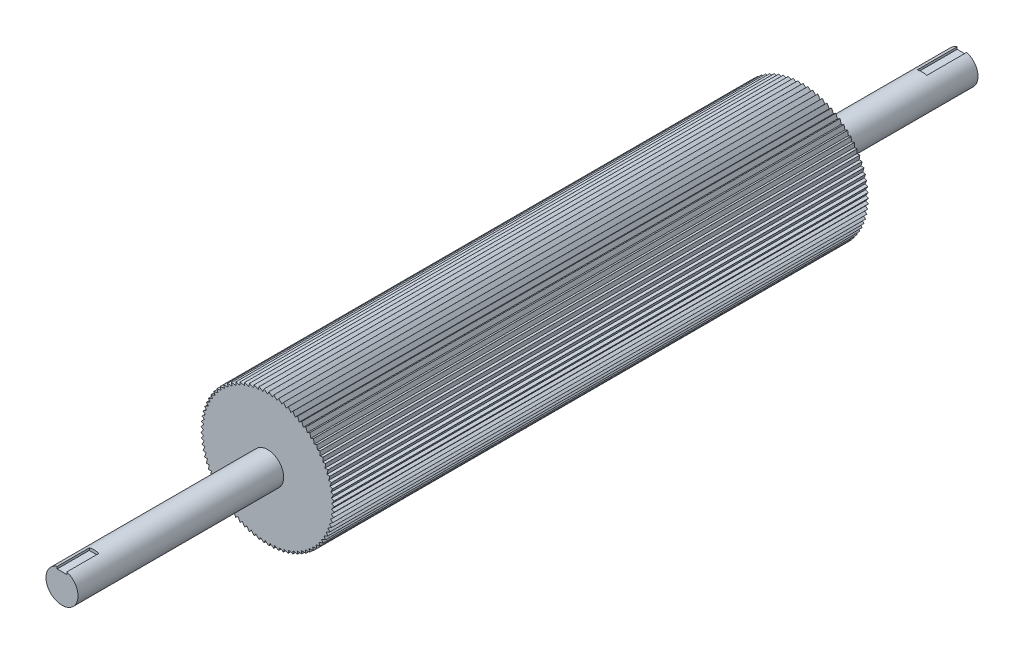
SolidWorks part; units mm, degrees
material "AISI 1020 Steel, Cold Rolled"
ref_plane "Front Plane" through (0, 0, 0) normal (0, 0, 1) x (1, 0, 0)
ref_plane "Top Plane" through (0, 0, 0) normal (0, 1, 0) x (1, 0, 0)
ref_plane "Right Plane" through (0, 0, 0) normal (1, 0, 0) x (0, 0, -1)
sketch "Sketch2" plane through (0, 0, 0) normal (0, 0, 1) x (1, 0, 0)
  circle A0 centre (0, 0) radius 125
  dimension "D1" = 250
extrude "Boss-Extrude1" add sketch "Sketch2" along normal mid plane 1000
sketch "Sketch3" plane through (0, 0, 500) normal (0, 0, 1) x (1, 0, 0)
  circle A0 centre (0, 0) radius 30
  dimension "D1" = 60
extrude "Boss-Extrude2" add sketch "Sketch3" along normal blind 385
sketch "Sketch4" plane through (0, 0, -500) normal (0, 0, -1) x (-1, 0, 0)
  circle A0 centre (0, 0) radius 30
  dimension "D1" = 60
extrude "Boss-Extrude3" add sketch "Sketch4" along normal blind 300
sketch "Sketch11" plane through (0, 0, 500) normal (0, 0, 1) x (1, 0, 0)
  line L0 (0, 14.8002) -> (0, 125) construction
sketch "Sketch12" plane through (0, 0, 885) normal (0, 0, 1) x (1, 0, 0)
  line L1 (-9, 24.5) -> (9, 24.5)
  line L2 (-9, 24.5) -> (-9, 35.5)
  line L3 (-9, 35.5) -> (9, 35.5)
  line L4 (9, 24.5) -> (9, 35.5)
  line L5 (-9, 24.5) -> (9, 35.5) construction
  line L6 (-9, 35.5) -> (9, 24.5) construction
  circle A0 centre (0, 0) radius 30 construction
  circle A1 centre (0, 0) radius 30 construction
  point P0 (0, 30)
  dimension "D1" = 18
  dimension "D2" = 5.5
extrude "Cut-Extrude5" cut sketch "Sketch12" against normal blind 60
sketch "Sketch15" plane through (0, 0, 500) normal (0, 0, 1) x (1, 0, 0)
  line L0 (0, 120) -> (2.3215, 124.9784)
  line L1 (0, 14.8002) -> (0, 125) construction
  line L2 (0, 120) -> (-6.8709, 124.811)
  circle A1 centre (0, 0) radius 125
  arc A2 (2.3215, 124.9784) -> (-6.8709, 124.811) centre (0, 0) ccw
  dimension "D4" = 120
  dimension "D2" = 25
  dimension "D3" = 55
  dimension "D1" = 0
extrude "Cut-Extrude6" cut sketch "Sketch15" against normal through all
pattern_circular "CirPattern1" count 85 over 360 about axis through (0, 0, 500) along (0, 0, -1) of "Cut-Extrude6" reverse direction yes
ref_plane "Plane1" through (0, 0, 50) normal (0, 0, 1) x (1, 0, 0)
sketch "Sketch16" plane through (0, 0, -800) normal (0, 0, -1) x (-1, 0, 0)
  line L1 (-9, 24.5) -> (9, 24.5)
  line L2 (-9, 24.5) -> (-9, 35.5)
  line L3 (-9, 35.5) -> (9, 35.5)
  line L4 (9, 24.5) -> (9, 35.5)
  line L5 (-9, 24.5) -> (9, 35.5) construction
  line L6 (-9, 35.5) -> (9, 24.5) construction
  circle A0 centre (0, 0) radius 30 construction
  circle A1 centre (0, 0) radius 30 construction
  point P0 (0, 30)
  dimension "D1" = 18
  dimension "D2" = 5.5
extrude "Cut-Extrude7" cut sketch "Sketch16" against normal blind 75
